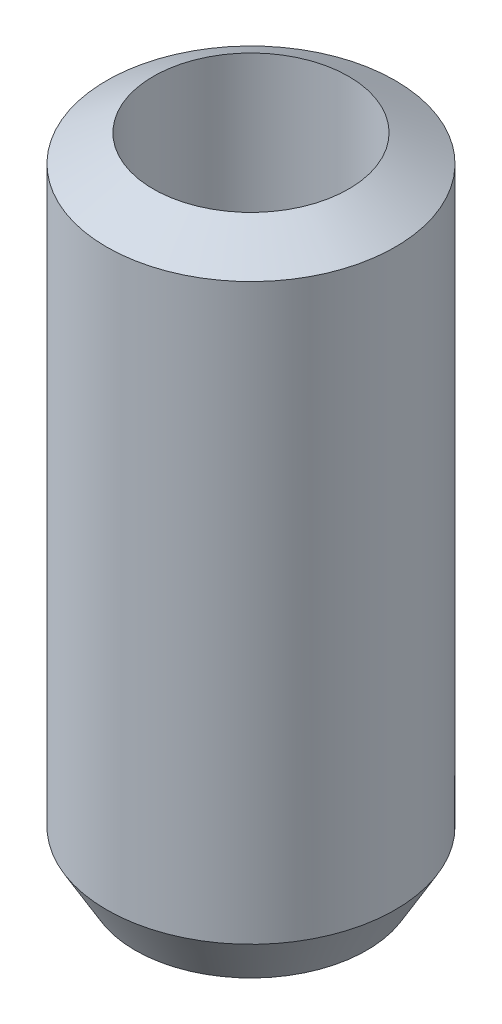
SolidWorks part; units mm, degrees
ref_plane "Front Plane" through (0, 0, 0) normal (0, 0, 1) x (1, 0, 0)
ref_plane "Top Plane" through (0, 0, 0) normal (0, 1, 0) x (1, 0, 0)
ref_plane "Right Plane" through (0, 0, 0) normal (1, 0, 0) x (0, 0, -1)
sketch "Sketch1" plane through (0, 0, 0) normal (0, 1, 0) x (1, 0, 0)
  circle A0 centre (0, 0) radius 20
  dimension "SHAFT_OD" = 40
extrude "Boss-Extrude1" add sketch "Sketch1" along normal blind 90.338
sketch "Sketch2" plane through (0, 0, 0) normal (0, 1, 0) x (1, 0, 0)
  circle A0 centre (0, 0) radius 13.5388
  dimension "BORE_D" = 27.0776
extrude "Cut-Extrude1" cut sketch "Sketch2" along normal through all
chamfer "Chamfer1" distance 3.9445 angle 60 2 edges at (0, 90.338, 20) (0, 0, 20) first distance on face at (0, 90.338, 20) first distance on face at (0, 0, 13.5388)
